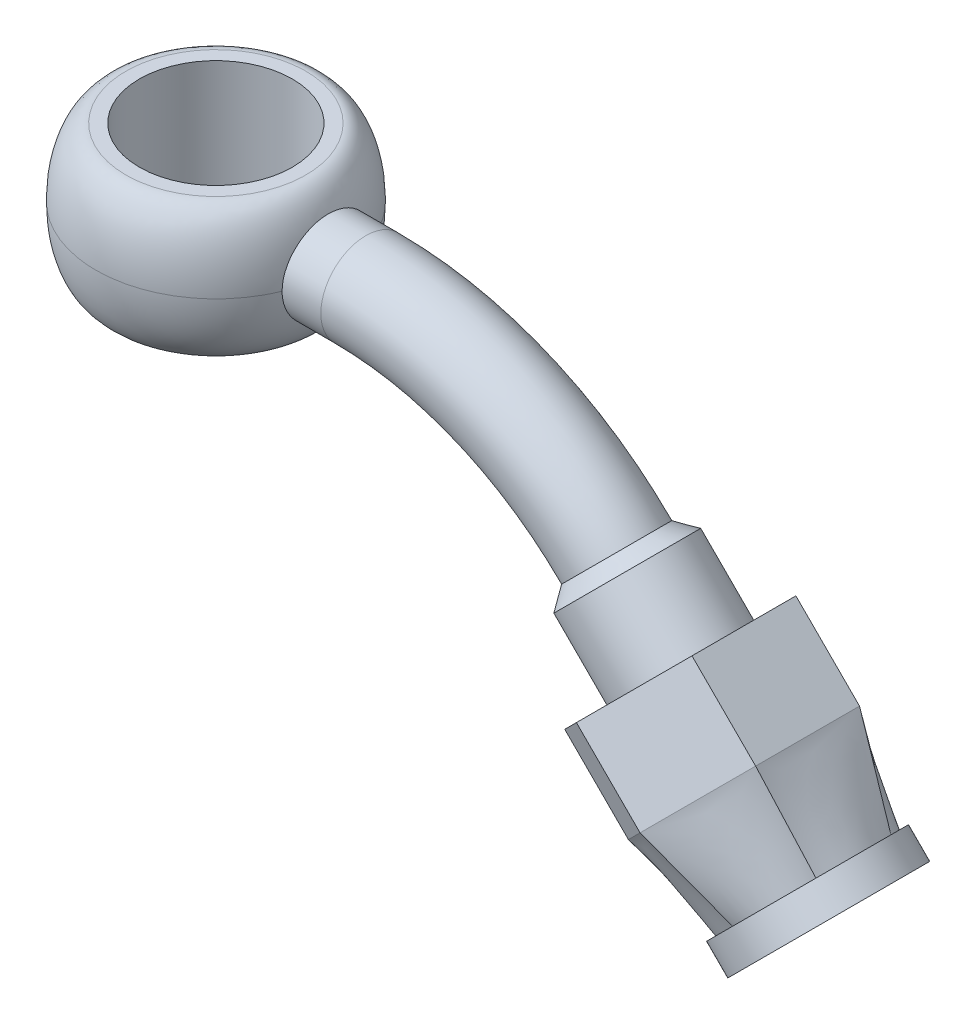
SolidWorks part; units mm, degrees
material "7075-T6 (SN)"
ref_plane "Płaszczyzna XY" through (0, 0, 0) normal (0, 0, 1) x (1, 0, 0)
ref_plane "Płaszczyzna XZ" through (0, 0, 0) normal (0, 1, 0) x (1, 0, 0)
ref_plane "Płaszczyzna YZ" through (0, 0, 0) normal (1, 0, 0) x (0, 0, -1)
sketch "Szkic1" plane through (0, 0, 0) normal (0, 1, 0) x (1, 0, 0)
  circle A0 centre (0, 0) radius 8
  dimension "D1" = 16
extrude "Dodanie-wyciągnięcie1" add sketch "Szkic1" along normal mid plane 9
sketch "Szkic2" plane through (0, 0, 0) normal (0, 0, 1) x (1, 0, 0)
  line L0 (0, 0) -> (10, 0)
  line L1 (26.7279, -6.9289) -> (41.0122, -21.2132) construction
  line L2 (41.0122, -21.2132) -> (34.5808, -27.6446) construction
  arc A0 (10, 0) -> (26.7279, -6.9289) centre (10, -23.6569) cw
  dimension "D1" = 10
  dimension "D2" = 44
  dimension "D3" = 45
  dimension "D4" = 14
sketch "Szkic3" plane through (0, 0, 0) normal (1, 0, 0) x (0, 0, -1)
  circle A0 centre (0, 0) radius 3
  circle A1 centre (0, 0) radius 1.5
  dimension "D1" = 6
  dimension "D2" = 3
sweep "Wyciągnięcie po ścieżce1" add profiles "Szkic3" path "Szkic2"
fillet "Zaokrąglenie1" radius 2 1 edges at (0, -4.5, 8)
fillet "Zaokrąglenie2" radius 4.5 1 edges at (0, 4.5, 8)
sketch "Szkic4" plane through (0, -4.5, 0) normal (0, -1, 0) x (1, 0, 0)
  circle A0 centre (0, 0) radius 5.1
  dimension "D1" = 10.2
extrude "Wytnij-wyciągnięcie1" cut sketch "Szkic4" against normal up to next
sketch "Szkic5" plane through (16.8284, -16.8284, 0) normal (0.7071, -0.7071, 0) x (0, 0, -1)
  circle A0 centre (0, 14) radius 4
  circle A1 centre (0, 14) radius 3
  circle A2 centre (0, 14) radius 3
  circle M2 centre (0, 14) radius 1.5
  circle M3 centre (0, 14) radius 3
  dimension "D2" = 8
  dimension "D1" = 0
extrude "Dodanie-wyciągnięcie2" add sketch "Szkic5" along normal blind 6 contours M3 M2 | A0 M3
sketch "Szkic6" plane through (21.0711, -21.0711, 0) normal (0.7071, -0.7071, 0) x (0, 0, -1)
  line L1 (6.9282, 14) -> (3.4641, 20)
  line L2 (3.4641, 20) -> (-3.4641, 20)
  line L3 (-3.4641, 20) -> (-6.9282, 14)
  line L4 (-6.9282, 14) -> (-3.4641, 8)
  line L5 (-3.4641, 8) -> (3.4641, 8)
  line L6 (3.4641, 8) -> (6.9282, 14)
  circle A0 centre (0, 14) radius 1.5 construction
  circle A1 centre (0, 14) radius 1.5
  circle A2 centre (0, 14) radius 6 construction
  dimension "D1" = 12
extrude "Dodanie-wyciągnięcie3" add sketch "Szkic6" along normal blind 6
ref_plane "Płaszczyzna1" through (29.5563, -29.5563, 0) normal (0.7071, -0.7071, 0) x (-0.7071, -0.7071, 0)
sketch "Szkic7" plane through (29.5563, -29.5563, 0) normal (0.7071, -0.7071, 0) x (-0.7071, -0.7071, 0)
  circle A0 centre (-14, 0) radius 5
  dimension "D1" = 10
sketch "Szkic8" plane through (25.3137, -25.3137, 0) normal (0.7071, -0.7071, 0) x (0, 0, -1)
  line L6 (3.4641, 8) -> (6.9282, 14)
  line L7 (6.9282, 14) -> (3.4641, 20)
  line L8 (3.4641, 20) -> (-3.4641, 20)
  line L9 (-3.4641, 20) -> (-6.9282, 14)
  line L10 (-6.9282, 14) -> (-3.4641, 8)
  line L11 (-3.4641, 8) -> (3.4641, 8)
  line L12 (3.4641, 8) -> (6.9282, 14)
  line L13 (6.9282, 14) -> (3.4641, 20)
  line L14 (3.4641, 20) -> (-3.4641, 20)
  line L15 (-3.4641, 20) -> (-6.9282, 14)
  line L16 (-6.9282, 14) -> (-3.4641, 8)
  line L17 (-3.4641, 8) -> (3.4641, 8)
  dimension "D1" = 0
loft "Wyciągnięcie po profilach1" add profiles "Szkic8", "Szkic7"
sketch "Szkic9" plane through (29.5563, -29.5563, 0) normal (0.7071, -0.7071, 0) x (0, 0, -1)
  circle A0 centre (0, 14) radius 5.5
  arc A6 (-5, 14) -> (-2.5, 9.6699) centre (0, 14) ccw
  arc A7 (-2.5, 9.6699) -> (2.5, 9.6699) centre (0, 14) ccw
  arc A8 (2.5, 9.6699) -> (5, 14) centre (0, 14) ccw
  arc A9 (5, 14) -> (2.5, 18.3301) centre (0, 14) ccw
  arc A10 (2.5, 18.3301) -> (-2.5, 18.3301) centre (0, 14) ccw
  arc A11 (-2.5, 18.3301) -> (-5, 14) centre (0, 14) ccw
  arc A12 (-5, 14) -> (-2.5, 9.6699) centre (0, 14) ccw
  arc A13 (-2.5, 9.6699) -> (2.5, 9.6699) centre (0, 14) ccw
  arc A14 (2.5, 9.6699) -> (5, 14) centre (0, 14) ccw
  arc A15 (5, 14) -> (2.5, 18.3301) centre (0, 14) ccw
  arc A16 (2.5, 18.3301) -> (-2.5, 18.3301) centre (0, 14) ccw
  arc A17 (-2.5, 18.3301) -> (-5, 14) centre (0, 14) ccw
  dimension "D2" = 11
  dimension "D1" = 0
extrude "Dodanie-wyciągnięcie4" add sketch "Szkic9" along normal blind 2
chamfer "Sfazowanie1" distance 1 angle 45 1 edges at (29.5563, -4.1005, 0)
sketch "Szkic10" plane through (30.9706, -30.9706, 0) normal (0.7071, -0.7071, 0) x (0, 0, -1)
  circle A0 centre (0, 14) radius 1.5
  circle A1 centre (0, 14) radius 5.5
  circle A2 centre (0, 14) radius 5.5
  dimension "D2" = 3
  dimension "D1" = 0
extrude "Wytnij-wyciągnięcie2" cut sketch "Szkic10" against normal up to next contours A0
ref_point "Punkt1"
ref_point "Punkt2"
